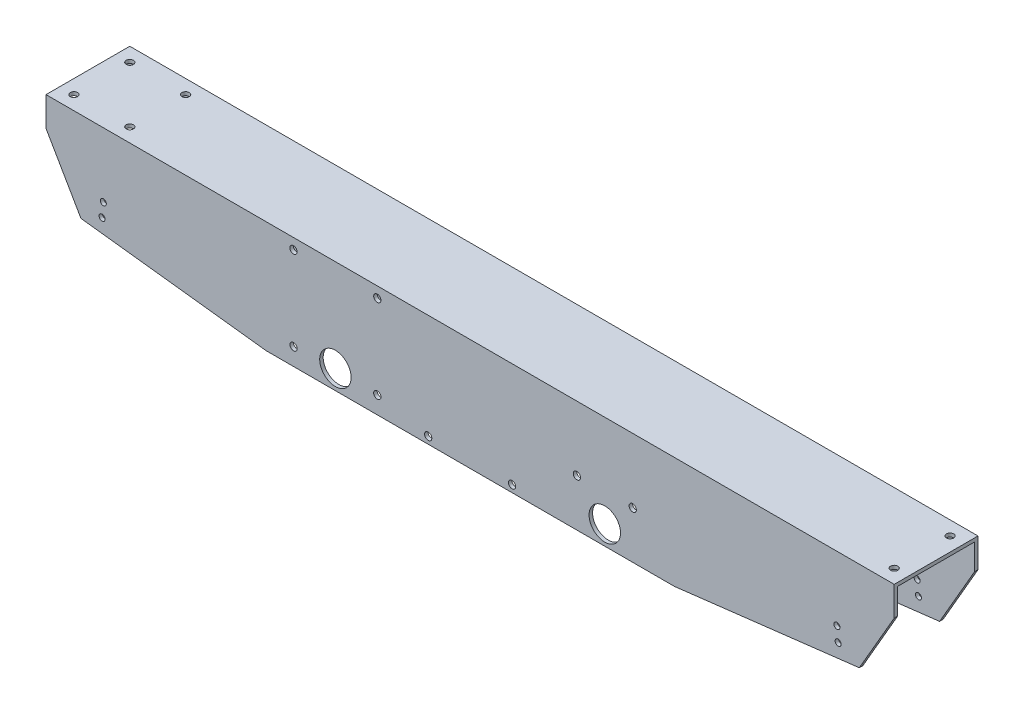
SolidWorks part; units mm, degrees
ref_plane "Front Plane" through (0, 0, 0) normal (0, 0, 1) x (1, 0, 0)
ref_plane "Top Plane" through (0, 0, 0) normal (0, 1, 0) x (1, 0, 0)
ref_plane "Right Plane" through (0, 0, 0) normal (1, 0, 0) x (0, 0, -1)
sketch "Sketch1" plane through (0, 0, 0) normal (1, 0, 0) x (0, 0, -1)
  line L0 (-34.925, 47.625) -> (-34.925, -47.625) construction
  line L1 (-38.1, 50.8) -> (38.1, 50.8)
  line L2 (-38.1, 50.8) -> (-38.1, -50.8)
  line L3 (-38.1, -50.8) -> (-34.925, -50.8)
  line L4 (38.1, 50.8) -> (38.1, -50.8)
  line L5 (-38.1, 50.8) -> (38.1, -50.8) construction
  line L6 (-38.1, -50.8) -> (38.1, 50.8) construction
  line L7 (34.925, 47.625) -> (34.925, -50.8)
  line L8 (-34.925, 47.625) -> (34.925, 47.625)
  line L9 (-34.925, 47.625) -> (-34.925, -50.8)
  line L10 (-34.925, -47.625) -> (34.925, -47.625) construction
  line L11 (34.925, 47.625) -> (34.925, -47.625) construction
  line L12 (-38.1, -50.8) -> (38.1, -50.8) construction
  line L13 (38.1, -50.8) -> (34.925, -50.8)
  point P0 (0, 0)
  dimension "D1" = 76.2
  dimension "D2" = 101.6
  dimension "D3" = 3.175
extrude "Boss-Extrude1" add sketch "Sketch1" along normal mid plane 771.4115
sketch "Sketch2" plane through (0, 0, 38.1) normal (0, 0, 1) x (1, 0, 0)
  line L0 (-405.1565, -33.274) -> (428.5144, -33.274) construction
  line L1 (385.7058, -50.8) -> (-385.7058, -50.8) construction
  line L3 (-122.5, 124.7315) -> (-122.5, -108.8261) construction
  line L4 (-122.5, 124.7315) -> (-122.5, -108.8261) construction
  line L7 (0, 107.4469) -> (0, -99.4956) construction
  line L9 (0, -41.91) -> (0, 41.91) construction
  line L13 (0, 50.8) -> (0, -55.872) construction
  line L14 (385.7058, 50.8) -> (-385.7058, 50.8) construction
  circle A0 centre (-333.5772, -7.874) radius 2.75
  circle A1 centre (334.7203, -20.574) radius 2.75
  circle A2 centre (333.5772, -7.874) radius 2.75
  circle A4 centre (-160.6, -35.12) radius 3.302
  circle A5 centre (-160.6, 41.08) radius 3.302
  circle A6 centre (-122.5, -33.274) radius 14.2875
  circle A7 centre (-334.7203, -20.574) radius 2.75
  circle A8 centre (-84.4, 41.08) radius 3.302
  circle A9 centre (-84.4, -35.12) radius 3.302
  circle A13 centre (122.5, -33.274) radius 14.2875
  point P16 (-122.5, -33.274)
  dimension "D1" = 17.526
  dimension "D2" = 212.6
  dimension "D3" = 212.6
  dimension "D4" = 122.5
  dimension "D7" = 25.4
  dimension "D8" = 12.7
  dimension "D9" = 76.2
  dimension "D10" = 76.2
  dimension "D11" = 76.2
  dimension "D12" = 6.604
  dimension "D13" = 15.68
  dimension "D14" = 38.1
extrude "Axles" cut sketch "Sketch2" against normal blind 141.732
sketch "Flanigan mounting holes" plane through (0, 0, 38.1) normal (0, 0, 1) x (1, 0, 0)
  line L0 (122.5, 79.5654) -> (122.5, -33.274) construction
  line L2 (97.1, 9.7703) -> (97.1, -58.1396) construction
  line L3 (385.7058, -50.8) -> (-385.7058, -50.8) construction
  line L4 (147.9, 11.4068) -> (147.9, -61.409) construction
  line L5 (147.9, -44.45) -> (97.1, -44.45) construction
  circle A1 centre (97.1, -7.87) radius 3.3
  circle A3 centre (147.9, -7.87) radius 3.3
  circle A5 centre (122.5, -33.274) radius 14.2875 construction
  point P4 (147.9, -7.87)
  point P5 (97.1, -7.87)
  point P6 (122.5, 14.36)
  dimension "D6" = 42.93
  dimension "D7" = 42.93
  dimension "D8" = 6.35
  dimension "D1" = 0
  dimension "D2" = 25.4
  dimension "D3" = 25.4
  dimension "D4" = 22.23
extrude "Flanigan mounting holes extrusion" cut sketch "Flanigan mounting holes" against normal through all
sketch "Sketch16" plane through (0, 0, 38.1) normal (0, 0, 1) x (1, 0, 0)
  line L0 (-353.9515, -30.8) -> (-185.7058, -50.8)
  line L1 (-385.7058, 50.8) -> (-385.7058, -50.8) construction
  line L2 (-385.7058, 24.2) -> (-353.9515, -30.8)
  line L3 (385.7058, -50.8) -> (-385.7058, -50.8) construction
  line L4 (-385.7058, 24.2) -> (-385.7058, -50.8)
  line L5 (-385.7058, -50.8) -> (-185.7058, -50.8)
  line L6 (0, 50.8) -> (0, -65.171) construction
  line L7 (0, -41.91) -> (0, 41.91) construction
  line L8 (0, 74.5999) -> (0, -74.6877) construction
  line L9 (385.7058, -50.8) -> (185.7058, -50.8)
  line L10 (385.7058, 24.2) -> (385.7058, -50.8)
  line L11 (385.7058, 24.2) -> (353.9515, -30.8)
  line L12 (353.9515, -30.8) -> (185.7058, -50.8)
  dimension "D1" = 60
extrude "Beveled ends" cut sketch "Sketch16" against normal blind 101.6
sketch "Sketch32" plane through (0, 0, -38.1) normal (0, 0, -1) x (-1, 0, 0)
  line L0 (0, 41.91) -> (0, -41.91) construction
  line L1 (-185.7058, -50.8) -> (185.7058, -50.8) construction
  line L3 (0, 54.6658) -> (0, -55.1985) construction
  circle A0 centre (-38.1, -44.45) radius 3.3
  circle A1 centre (38.1, -44.45) radius 3.3
  point P8 (38.1, -44.45)
  dimension "D1" = 6.6
  dimension "D3" = 6.35
  dimension "D2" = 38.1
extrude "Belt shield holes" cut sketch "Sketch32" against normal through all
sketch "Sketch37" plane through (0, 50.8, 0) normal (0, 1, 0) x (1, 0, 0)
  line L0 (385.7058, 38.1) -> (-385.7058, 38.1) construction
  line L1 (385.7058, 38.1) -> (385.7058, -38.1) construction
  line L2 (385.7058, -38.1) -> (-385.7058, -38.1) construction
  line L3 (-385.7058, 38.1) -> (-385.7058, -38.1) construction
  circle A0 centre (373.0058, 25.4) radius 3.3
  circle A1 centre (373.0058, -25.4) radius 3.3
  circle A2 centre (-322.2058, 25.4) radius 3.3
  circle A3 centre (-322.2058, -25.4) radius 3.3
  circle A4 centre (-373.0058, 25.4) radius 3.3
  circle A5 centre (-373.0058, -25.4) radius 3.3
  dimension "D1" = 6.6
  dimension "D2" = 12.7
  dimension "D3" = 12.7
  dimension "D4" = 63.5
  dimension "D6" = 12.7
  dimension "D10" = 12.7
extrude "Top holes" cut sketch "Sketch37" against normal through all
